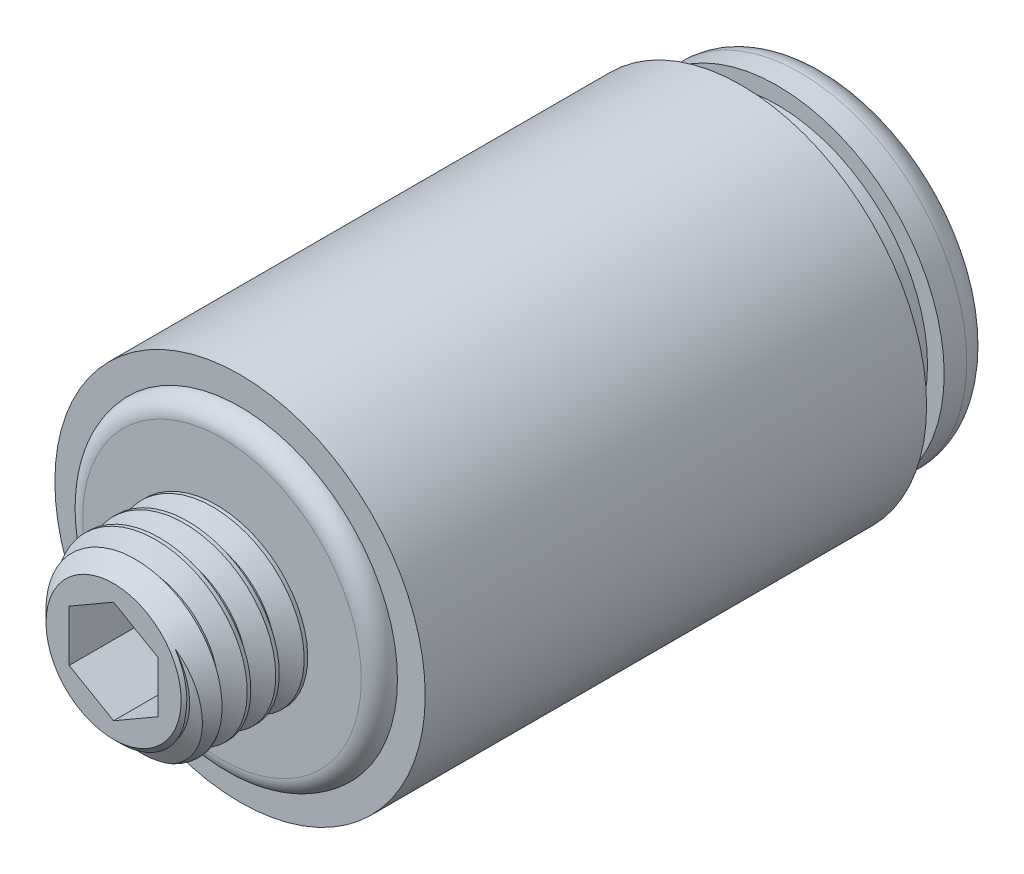
SolidWorks part; units mm, degrees
ref_plane "Front Plane" through (0, 0, 0) normal (0, 0, 1) x (1, 0, 0)
ref_plane "Top Plane" through (0, 0, 0) normal (0, 1, 0) x (1, 0, 0)
ref_plane "Right Plane" through (0, 0, 0) normal (1, 0, 0) x (0, 0, -1)
sketch "Sketch8" plane through (0, 0, 0) normal (1, 0, 0) x (0, 0, -1)
  line L0 (18.669, 4.6863) -> (19.304, 4.6863)
  line L1 (3.556, 5.207) -> (17.653, 5.207)
  line L2 (3.556, 5.207) -> (3.556, 3.175)
  line L3 (3.556, 3.175) -> (19.685, 3.175)
  line L4 (20.066, 3.9243) -> (20.066, 3.556)
  line L6 (17.653, 5.207) -> (17.653, 4.2177)
  line L7 (17.653, 4.2177) -> (18.669, 4.2177)
  line L8 (18.669, 4.6863) -> (18.669, 4.2177)
  line L10 (0, 0) -> (20.066, 0) construction
  line L12 (19.685, 3.175) -> (20.066, 3.556)
  line L13 (3.556, 0) -> (3.556, 5.207) construction
  line L14 (0, -2.5) -> (0, 2.5) construction
  arc A0 (19.304, 4.6863) -> (20.066, 3.9243) centre (19.304, 3.9243) cw
  point P0 (10.033, 0)
  point P1 (20.066, 3.175)
  point P20 (20.066, 4.6863)
  dimension "D4" = 0.762
  dimension "D1" = 1.397
  dimension "tube od" = 6.35
  dimension "D2" = 1.016
  dimension "D3" = 8.4353
  dimension "D5" = 10.414
  dimension "D6" = 9.3726
  dimension "D8" = 16.51
  dimension "D9" = 3.556
  dimension "D10" = 5
revolve "Revolve1" add sketch "Sketch8" angle 360 about L10
sketch "Sketch9" plane through (0, 0, 0) normal (1, 0, 0) x (0, 0, -1)
  line L0 (3.556, 0) -> (0, 0)
  line L1 (0, 0) -> (0, 2.5)
  line L2 (0, 2.5) -> (3.556, 2.5)
  line L3 (3.556, 5.207) -> (3.556, 3.175) construction
  line L4 (3.556, 2.5) -> (3.556, 0)
revolve "Revolve2" add sketch "Sketch9" angle 360 about L10
sketch "Sketch10" plane through (0, 0, -3.556) normal (0, 0, -1) x (-1, 0, 0)
  circle A1 centre (0, 0) radius 2.5
  circle A2 centre (0, 0) radius 2.5
  dimension "D1" = 0
curve "Helix/Spiral1" pitch 0.8 height 4.356 turns 5.445
sketch "Sketch11" plane through (0, 0, 0) normal (1, 0, 0) x (0, 0, -1)
  line L0 (3.556, 2.5) -> (4.256, 2.5)
  line L1 (4.256, 2.5) -> (3.956, 1.9804)
  line L2 (3.956, 1.9804) -> (3.856, 1.9804)
  line L3 (3.856, 1.9804) -> (3.556, 2.5)
  line L5 (3.906, 1.9804) -> (3.906, 2.5) construction
  line L6 (4.106, 2.2402) -> (3.706, 2.2402) construction
  dimension "D1" = 0.1
  dimension "D2" = 0.4
  dimension "D3" = 60
chamfer "Chamfer1" distance 0.6 angle 45 1 edges at (2.5, 0, 0)
sweep "Cut-Sweep2" cut profiles "Sketch11" path "Helix/Spiral1"
sketch "Sketch14" plane through (0, 0, 0) normal (1, 0, 0) x (0, 0, -1)
  line L0 (3.556, 0) -> (3.556, 4.4259)
  line L1 (3.556, 5.207) -> (3.556, -5.207) construction
  line L2 (3.556, 4.4259) -> (4.064, 4.4259) construction
  line L3 (3.556, 4.4259) -> (3.048, 4.4259) construction
  line L4 (3.048, 4.4259) -> (3.048, 0) construction
  line L5 (3.048, 0) -> (3.556, 0)
  line L6 (3.556, 4.4259) -> (3.556, -4.4259) construction
  line L7 (3.048, 3.9179) -> (3.048, 0)
  arc A0 (3.556, 4.4259) -> (3.048, 3.9179) centre (3.556, 3.9179) ccw
  dimension "D1" = 0.508
  dimension "D2" = 8.8519
revolve "Revolve3" add sketch "Sketch14" angle 360 about L5
sketch "Sketch12" plane through (0, 0, 0) normal (0, 0, 1) x (1, 0, 0)
  line L0 (0, -2.5) -> (0, 2.5) construction
  line L1 (0, 1.4434) -> (-1.25, 0.7217)
  line L2 (-1.25, 0.7217) -> (-1.25, -0.7217)
  line L3 (-1.25, -0.7217) -> (0, -1.4434)
  line L4 (0, -1.4434) -> (1.25, -0.7217)
  line L5 (1.25, -0.7217) -> (1.25, 0.7217)
  line L6 (1.25, 0.7217) -> (0, 1.4434)
  line L7 (0, 0) -> (0, 5.207) construction
  circle A0 centre (0, 0) radius 1.25 construction
  dimension "D1" = 2.5
extrude "Cut-Extrude1" cut sketch "Sketch12" against normal through all
equation "\"D6@Sketch8\" = \"D5@Sketch8\"*.9"
equation "\"D3@Sketch8\" = \"D6@Sketch8\"*.9"
equation "\"D3@Helix/Spiral1\"= \"D9@Sketch8\" + \"D4@Helix/Spiral1\""
equation "\"D1@Sketch11\"= \"D4@Helix/Spiral1\" * .125"
equation "\"D2@Sketch11\"= \"D4@Helix/Spiral1\" * .5"
equation "\"D1@Chamfer1\"= \"D4@Helix/Spiral1\" * .75"
equation "\"D2@Sketch14\"=\"D5@Sketch8\" * .85"
